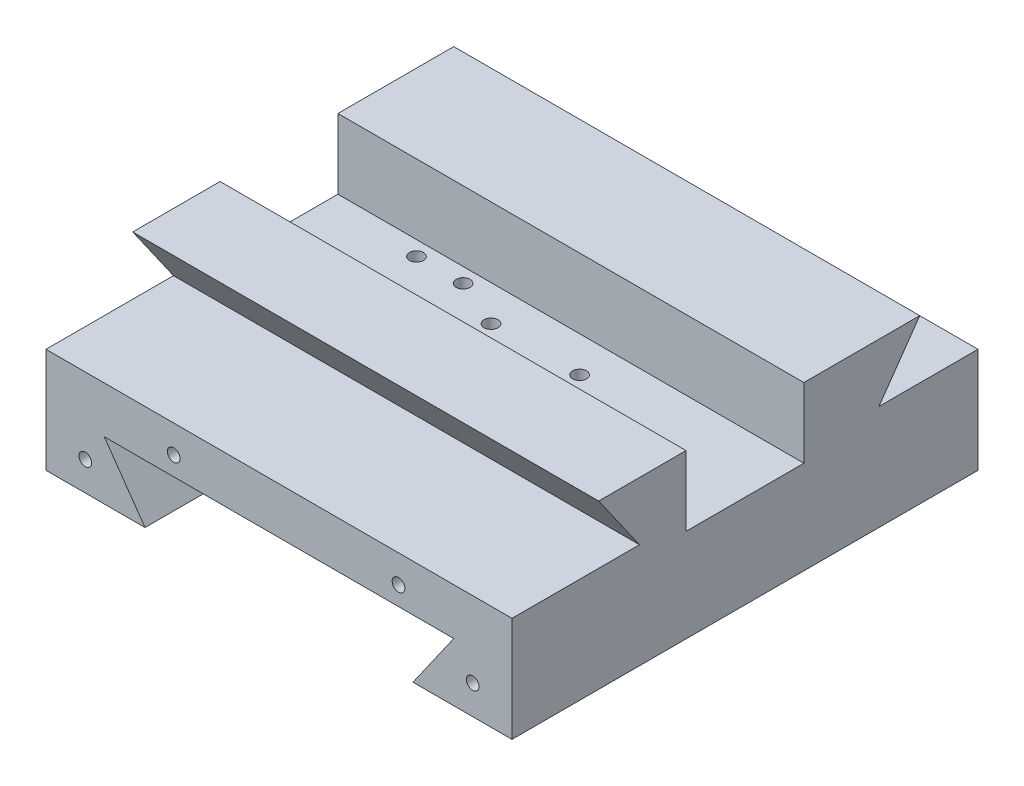
SolidWorks part; units mm, degrees
material "Ductile Iron"
ref_plane "Front Plane" through (0, 0, 0) normal (0, 0, 1) x (1, 0, 0)
ref_plane "Top Plane" through (0, 0, 0) normal (0, 1, 0) x (1, 0, 0)
ref_plane "Right Plane" through (0, 0, 0) normal (1, 0, 0) x (0, 0, -1)
sketch "female-dovetail-profile" plane through (0, 0, 0) normal (0, 0, 1) x (1, 0, 0)
  line L0 (0, 0) -> (26.9908, 0)
  line L1 (26.9908, 0) -> (15.875, 15.875)
  line L2 (15.875, 15.875) -> (111.125, 15.875)
  line L3 (111.125, 15.875) -> (100.0092, 0)
  line L4 (100.0092, 0) -> (127, 0)
  line L5 (127, 0) -> (127, 44.45)
  line L6 (127, 44.45) -> (0, 44.45)
  line L7 (0, 44.45) -> (0, 0)
  dimension "D1" = 127
  dimension "D2" = 95.25
  dimension "D3" = 55
  dimension "D4" = 55
  dimension "D5" = 15.875
  dimension "D6" = 44.45
extrude "x-carriage-extrude" add sketch "female-dovetail-profile" along normal blind 127
sketch "male-dovetail-shoulder-profile" plane through (127, 0, 0) normal (1, 0, 0) x (0, 0, -1)
  line L0 (-127, 28.575) -> (-100.0092, 28.575) construction
  line L1 (-100.0092, 28.575) -> (-111.125, 44.45) construction
  line L2 (-111.125, 44.45) -> (-127, 44.45) construction
  line L3 (-127, 44.45) -> (-127, 28.575)
  line L4 (0, 0) -> (0, 44.45)
  line L5 (0, 44.45) -> (-127, 44.45)
  line L6 (-127, 44.45) -> (-127, 0)
  line L7 (-127, 0) -> (0, 0)
  line L8 (0, 0) -> (0, 44.45) construction
  line L9 (0, 44.45) -> (-127, 44.45) construction
  line L10 (-127, 44.45) -> (-127, 0) construction
  line L11 (-127, 0) -> (0, 0) construction
  line L12 (-15.875, 44.45) -> (0, 44.45) construction
  line L13 (0, 44.45) -> (0, 28.575)
  line L14 (0, 28.575) -> (-26.9908, 28.575)
  line L15 (-26.9908, 28.575) -> (-15.875, 44.45)
  line L16 (-15.875, 44.45) -> (0, 44.45)
  line L17 (-127, 28.575) -> (-92.2573, 28.575)
  line L18 (-92.2573, 28.575) -> (-103.3731, 44.45)
  line L19 (-103.3731, 44.45) -> (-127, 44.45)
  dimension "D2" = 55
  dimension "D3" = 55
  dimension "D4" = 95.25
  dimension "D5" = 15.875
  dimension "D6" = 6.35
  dimension "D1" = 0
extrude "y-guide-cut-extrude" cut sketch "male-dovetail-shoulder-profile" against normal through all
sketch "Sketch1" plane through (0, 0, 0) normal (1, 0, 0) x (0, 0, -1)
  line L0 (-63.5, 0) -> (-63.5, 44.45) construction
  line L1 (-127, 0) -> (0, 0) construction
  line L2 (-103.3731, 44.45) -> (-15.875, 44.45) construction
  line L4 (-79.5563, 44.45) -> (-47.4437, 44.45)
  line L5 (-79.5563, 44.45) -> (-79.5563, 25.4)
  line L6 (-79.5563, 25.4) -> (-47.4437, 25.4)
  line L7 (-47.4437, 44.45) -> (-47.4437, 25.4)
  circle A0 centre (-63.5, 34.925) radius 18.669 construction
  point P10 (-63.5, 44.45)
  dimension "D2" = 37.338
  dimension "D1" = 19.05
extrude "Cut-Extrude1" cut sketch "Sketch1" along normal through all
hole_wizard "#10-24 Tapped Hole1" positions "Sketch3" profile "Sketch2" tap size "#10-24" standard "ANSI Inch" end condition up to next
sketch "Sketch3" plane through (0, 25.4, 0) normal (0, 1, 0) x (1, 0, 0)
  line L8 (0, -47.4437) -> (0, -79.5563)
  line L9 (0, -79.5563) -> (127, -79.5563)
  line L10 (127, -79.5563) -> (127, -47.4437)
  line L11 (127, -47.4437) -> (0, -47.4437)
  line L12 (0, -47.4437) -> (0, -79.5563)
  line L13 (0, -79.5563) -> (127, -79.5563)
  line L14 (127, -79.5563) -> (127, -47.4437)
  line L15 (127, -47.4437) -> (0, -47.4437)
  line L16 (0, -63.5) -> (127, -63.5) construction
  line L18 (31.75, -52.0157) -> (31.75, -84.1283) construction
  line L21 (38.1, -51.435) -> (25.4, -51.435) construction
  line L22 (38.1, -51.435) -> (38.1, -75.565) construction
  line L23 (38.1, -75.565) -> (25.4, -75.565) construction
  line L24 (25.4, -51.435) -> (25.4, -75.565) construction
  line L37 (51.435, -57.15) -> (75.565, -57.15) construction
  line L38 (75.565, -57.15) -> (75.565, -69.85) construction
  line L39 (75.565, -69.85) -> (51.435, -69.85) construction
  line L40 (51.435, -69.85) -> (51.435, -57.15) construction
  line L41 (51.435, -57.15) -> (75.565, -57.15) construction
  line L42 (75.565, -57.15) -> (75.565, -69.85) construction
  line L44 (63.5, -47.4437) -> (63.5, -79.5563) construction
  point P0 (25.4, -51.435)
  point P2 (25.4, -75.565)
  point P4 (38.1, -75.565)
  point P6 (38.1, -51.435)
  point P118 (38.1, -63.5)
  point P119 (31.75, -75.565)
  point P154 (51.435, -57.15)
  point P156 (75.565, -57.15)
  point P158 (75.565, -69.85)
  point P160 (51.435, -69.85)
  point P198 (63.5, -57.15)
  point P199 (75.565, -63.5)
  dimension "D2" = 24.13
  dimension "D3" = 12.7
  dimension "D4" = 31.75
  dimension "D5" = 24.13
  dimension "D6" = 12.7
  dimension "D1" = 0
sketch "Sketch2" plane through (25.4, 25.4, 51.435) normal (1, 0, 0) x (0, 0, 1)
  line L0 (0, 0) -> (0, 9.525)
  line L1 (0, 9.525) -> (1.8986, 9.525)
  line L2 (1.8986, 9.525) -> (1.8986, 0)
  line L5 (1.8986, 0) -> (0, 0)
  line L11 (0, -6.35) -> (0, 107.95) construction
  dimension "Thru Tap Drill Dia." = 3.7973
  dimension "Thru Tap Drill Depth" = 9.525
cosmetic thread "Hole Thread1" parameters "D2"=4.826
cosmetic thread "Hole Thread2" parameters "D2"=4.826
cosmetic thread "Hole Thread3" parameters "D2"=4.826
cosmetic thread "Hole Thread4" parameters "D2"=4.826
cosmetic thread "Hole Thread5" parameters "D2"=4.826
cosmetic thread "Hole Thread6" parameters "D2"=4.826
cosmetic thread "Hole Thread7" parameters "D2"=4.826
cosmetic thread "Hole Thread8" parameters "D2"=4.826
hole_wizard "#8-32 Tapped Hole1" positions "Sketch4" profile "Sketch5" tap size "#8-32" standard "ANSI Inch"
sketch "Sketch4" plane through (0, -15.875, 127) normal (0, 0, 1) x (1, 0, 0)
  line L0 (34.8034, 41.275) -> (34.8034, 32.512) construction
  line L3 (96.0726, 41.275) -> (96.0726, 32.512) construction
  line L6 (111.125, 31.75) -> (127, 31.75) construction
  line L7 (15.875, 31.75) -> (0, 31.75) construction
  line L8 (7.9375, 31.75) -> (13.4954, 15.875) construction
  line L9 (119.0625, 31.75) -> (113.5046, 15.875) construction
  line L22 (127, 44.45) -> (0, 44.45) construction
  line L23 (0, 44.45) -> (0, 15.875) construction
  line L24 (0, 15.875) -> (26.9908, 15.875) construction
  line L25 (26.9908, 15.875) -> (15.875, 31.75) construction
  line L26 (15.875, 31.75) -> (111.125, 31.75) construction
  line L27 (111.125, 31.75) -> (100.0092, 15.875) construction
  line L28 (100.0092, 15.875) -> (127, 15.875) construction
  line L29 (127, 15.875) -> (127, 44.45) construction
  point P0 (10.7164, 23.8125)
  point P1 (34.8034, 36.8935)
  point P2 (96.0726, 36.8935)
  point P3 (116.2836, 23.8125)
cosmetic thread "Hole Thread9" parameters "D1"=8.382, "D2"=4.1656
cosmetic thread "Hole Thread10" parameters "D1"=8.382, "D2"=4.1656
cosmetic thread "Hole Thread11" parameters "D1"=8.382, "D2"=4.1656
cosmetic thread "Hole Thread12" parameters "D1"=8.382, "D2"=4.1656
sketch "Sketch5" plane through (10.7164, 7.9375, 127) normal (1, 0, 0) x (0, -1, 0)
  line L0 (0, 0) -> (0, 13.3822)
  line L1 (0, 13.3822) -> (1.7272, 12.3444)
  line L2 (1.7272, 12.3444) -> (1.7272, 0)
  line L3 (1.7272, 0) -> (0, 0)
  line L4 (0, 13.3822) -> (-1.7272, 12.3444) construction
  line L5 (0, -6.35) -> (0, 107.95) construction
  dimension "Tap Drill Dia." = 3.4544
  dimension "Tap Drill Depth" = 12.3444
  dimension "Drill Angle" = 118
hole_wizard "#8-32 Tapped Hole2" positions "Sketch6" profile "Sketch7" tap size "#8-32" standard "ANSI Inch"
sketch "Sketch6" plane through (0, -15.875, 0) normal (0, 0, -1) x (-1, 0, 0)
  point P0 (-10.7164, 23.8125)
  point P1 (-34.8034, 36.8935)
  point P2 (-96.0726, 36.8935)
  point P3 (-116.2836, 23.8125)
cosmetic thread "Hole Thread13" parameters "D1"=8.382, "D2"=4.1656
cosmetic thread "Hole Thread14" parameters "D1"=8.382, "D2"=4.1656
cosmetic thread "Hole Thread15" parameters "D1"=8.382, "D2"=4.1656
cosmetic thread "Hole Thread16" parameters "D1"=8.382, "D2"=4.1656
sketch "Sketch7" plane through (10.7164, 7.9375, 0) normal (1, 0, 0) x (0, 1, 0)
  line L0 (0, 0) -> (0, 13.4838)
  line L1 (0, 13.4838) -> (1.7272, 12.446)
  line L2 (1.7272, 12.446) -> (1.7272, 0)
  line L5 (1.7272, 0) -> (0, 0)
  line L10 (0, 13.4838) -> (-1.7272, 12.446) construction
  line L11 (0, -6.35) -> (0, 107.95) construction
  dimension "Tap Drill Dia." = 3.4544
  dimension "Tap Drill Depth" = 12.446
  dimension "Drill Angle" = 118
hole_wizard "gib screw 1/4-20 Tapped Hole1" positions "Sketch9" profile "Sketch8" tap size "1/4-20" standard "ANSI Inch" end condition up to next
sketch "Sketch9" plane through (0, 0, 0) normal (-1, 0, 0) x (0, 0, 1)
  line L0 (127, 15.875) -> (0, 15.875) construction
  line L1 (127, 15.875) -> (0, 15.875) construction
  line L2 (63.5, 15.875) -> (63.5, 0) construction
  line L3 (127, 0) -> (0, 0) construction
  line L4 (0, 7.9375) -> (127, 7.9375) construction
  line L5 (0, 28.575) -> (0, 0) construction
  line L6 (127, 28.575) -> (127, 0) construction
  line L7 (25.4, 7.9375) -> (63.5, 7.9375) construction
  point P0 (25.4, 7.9375)
  point P16 (63.5, 7.9375)
  point P22 (63.5, 7.9375)
  point P23 (101.6, 7.9375)
  dimension "D1" = 38.1
  dimension "D2" = 3
sketch "Sketch8" plane through (0, 7.9375, 25.4) normal (0, 1, 0) x (0, 0, 1)
  line L0 (0, 0) -> (0, 21.4329)
  line L1 (0, 21.4329) -> (2.5527, 21.4329)
  line L2 (2.5527, 21.4329) -> (2.5527, 0)
  line L5 (2.5527, 0) -> (0, 0)
  line L11 (0, -6.35) -> (0, 107.95) construction
  dimension "Thru Tap Drill Dia." = 5.1054
  dimension "Thru Tap Drill Depth" = 21.4329
cosmetic thread "Hole Thread17" parameters "D2"=6.35
cosmetic thread "Hole Thread18" parameters "D2"=6.35
cosmetic thread "Hole Thread19" parameters "D2"=6.35
equation "\"dovetail-angle\" = 55"
equation "\"dovetail-stock-width\" = 5"
equation "\"dovetail-stock-height\" = 1.25"
equation "\"dovetail-depth\" = 0.5 * \"dovetail-stock-height\""
equation "\"dovetail-throat-width\" = \"dovetail-stock-width\" - (2 * \"dovetail-depth\")"
equation "\"delta-x\" = 6"
equation "\"delta-y\" = 3"
equation "\"delta-z\"= 2.5"
equation "\"gib-thickness\" = 0.25"
equation "\"x-slide-length\" = \"dovetail-stock-width\" + \"delta-x\""
equation "\"y-slide-length\" = \"dovetail-stock-width\" + \"delta-y\""
equation "\"dog-point-diam\" = .149"
equation "\"D1@female-dovetail-profile\"=\"dovetail-stock-width\""
equation "\"D2@female-dovetail-profile\"=\"dovetail-throat-width\""
equation "\"D3@female-dovetail-profile\"=\"dovetail-angle\""
equation "\"D4@female-dovetail-profile\"=\"dovetail-angle\""
equation "\"D5@female-dovetail-profile\"=\"dovetail-depth\""
equation "\"D1@x-carriage-extrude\"=\"dovetail-stock-width\""
equation "\"dog-point-length\" = .067"
equation "\"dovetail-double-height\" = 2 * \"dovetail-depth\" + 0.5"
equation "\"D6@female-dovetail-profile\"=\"dovetail-double-height\""
equation "\"D2@male-dovetail-shoulder-profile\"=\"dovetail-angle\""
equation "\"D3@male-dovetail-shoulder-profile\"=\"dovetail-angle\""
equation "\"D4@male-dovetail-shoulder-profile\"=\"dovetail-throat-width\""
equation "\"D5@male-dovetail-shoulder-profile\"=\"dovetail-depth\""
equation "\"D6@male-dovetail-shoulder-profile\"=\"gib-thickness\""
equation "\"acme-major-diam\" = .5"
equation "\"acme-pitch-diam\" = 0.45"
equation "\"acme-minor-diam\" = 0.4"
equation "\"acme-nut-od\" = 1.47"
equation "\"acme-nut-length\" = 1"
equation "\"acme-nut-trim-height\" = .75"
equation "\"screw-bearing-od\" = 0.5"
equation "\"screw-bearing-length\" = .25"
equation "\"screw-bearing-id\" = .375"
equation "\"end-plate-thickness\" = \"screw-bearing-length\""
equation "\"screw-add-length\" = 2 * \"end-plate-thickness\" + 1 + 0.5"
equation "\"x-screw-length\" = \"x-slide-length\" + \"screw-add-length\""
equation "\"y-screw-length\" = \"y-slide-length\" + \"screw-add-length\""
equation "\"D1@Sketch1\"=\"acme-nut-trim-height\""
equation "\"D2@Sketch1\"=\"acme-nut-od\""
equation "\"acme-nut-mount-hole-space-horz\" = 0.95"
equation "\"acme-nut-mount-hole-space-vert\" = 0.5 * \"acme-nut-length\""
equation "\"D2@Sketch3\"=\"acme-nut-mount-hole-space-horz\""
equation "\"D3@Sketch3\"=\"acme-nut-mount-hole-space-vert\""
equation "\"D4@Sketch3\"=\"dovetail-stock-width\"/4"
equation "\"D5@Sketch3\"=\"acme-nut-mount-hole-space-horz\""
equation "\"D6@Sketch3\"=\"acme-nut-mount-hole-space-vert\""
